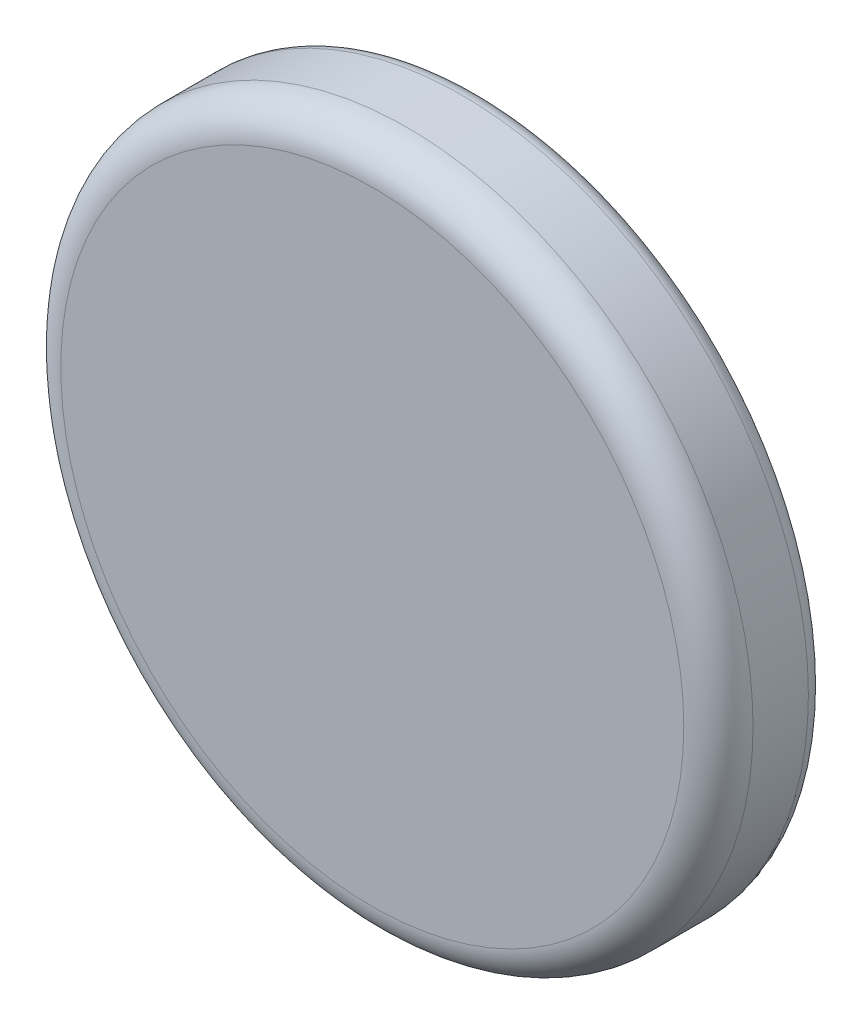
SolidWorks part; units mm, degrees
ref_plane "前视基准面" through (0, 0, 0) normal (0, 0, 1) x (1, 0, 0)
ref_plane "上视基准面" through (0, 0, 0) normal (0, 1, 0) x (1, 0, 0)
ref_plane "右视基准面" through (0, 0, 0) normal (1, 0, 0) x (0, 0, -1)
other "Configuration Table"
sketch "草图1" plane through (0, 0, 0) normal (0, 0, 1) x (1, 0, 0)
  line L0 (-2.5, 0) -> (2.5, 0) construction
  line L1 (0, -2.5) -> (0, 2.5) construction
  line L8 (-0.3703, -2) -> (0.3703, -2)
  line L13 (-0.3703, -2) -> (-0.3703, -0.3359)
  line L14 (-0.3703, 2) -> (0.3703, 2)
  line L54 (0.3703, -2) -> (0.3703, -0.3359)
  line L55 (-0.3703, -2) -> (0.3703, 2) construction
  line L56 (-0.3703, 2) -> (0.3703, -2) construction
  line L57 (-2, -0.3359) -> (-0.3703, -0.3359)
  line L58 (-2, -0.3359) -> (-2, 0.3359)
  line L59 (-2, 0.3359) -> (-0.3703, 0.3359)
  line L60 (2, -0.3359) -> (2, 0.3359)
  line L61 (-2, -0.3359) -> (2, 0.3359) construction
  line L62 (-2, 0.3359) -> (2, -0.3359) construction
  line L70 (-0.3703, 0.3359) -> (-0.3703, 2)
  line L71 (0.3703, 0.3359) -> (0.3703, 2)
  line L72 (0.3703, 0.3359) -> (2, 0.3359)
  line L73 (0.3703, -0.3359) -> (2, -0.3359)
  line L90 (0.5703, 0.5359) -> (0.5703, 2.2)
  line L91 (-0.5703, 2.2) -> (0.5703, 2.2)
  line L92 (-0.5703, 0.5359) -> (-0.5703, 2.2)
  line L93 (-2.2, 0.5359) -> (-0.5703, 0.5359)
  line L94 (-2.2, -0.5359) -> (-2.2, 0.5359)
  line L95 (-2.2, -0.5359) -> (-0.5703, -0.5359)
  line L96 (-0.5703, -2.2) -> (-0.5703, -0.5359)
  line L97 (-0.5703, -2.2) -> (0.5703, -2.2)
  line L98 (0.5703, -2.2) -> (0.5703, -0.5359)
  line L99 (0.5703, -0.5359) -> (2.2, -0.5359)
  line L100 (2.2, -0.5359) -> (2.2, 0.5359)
  line L101 (0.5703, 0.5359) -> (2.2, 0.5359)
  circle A5 centre (0, 0) radius 10
  circle A7 centre (0, 0) radius 9
  circle A9 centre (0, 0) radius 2.5
  point P5 (0, 0)
  point P6 (0, 0)
  point P8 (0, 0)
  point P10 (0, 0)
  dimension "D1" = 5
  dimension "D7" = 20
  dimension "D3" = 4
  dimension "D4" = 0.2
  dimension "D2" = 4
  dimension "D5" = 1.0717
  dimension "D9" = 1
extrude "凸台-拉伸19" add sketch "草图1" against normal blind 2.1 contours A9 L90 L101 L100 L99 L98 L97 L96 L95 L94 L93 L92 L91 region at (-2.4293, 0, 0)
extrude "凸台-拉伸20" add sketch "草图1<24>" along normal blind 1 contours L54 L73 L60 L72 L71 L14 L70 L59 L58 L57 L13 L8 | L101 L90 L91 L92 L93 L94 L95 L96 L97 L98 L99 L100 L73 L54 L8 L13 L57 L58 L59 L70 L14 L71 L72 L60 | A9 L90 L101 L100 L99 L98 L97 L96 L95 L94 L93 L92 L91 | A7 A9 region at (0, 0, 0) region at (1.3852, 0.4736, 0) region at (-8.7454, 0, 0) region at (-2.4293, 0, 0)
sketch "草图1<24>" plane through (0, 0, 0) normal (0, 0, 1) x (1, 0, 0) same geometry as "草图1"
extrude "凸台-拉伸21" add sketch "草图1<25>" along normal blind 1 and the other way blind 2.1 contours A5 A7 region at (-9.7172, 0, 0)
sketch "草图1<25>" plane through (0, 0, 0) normal (0, 0, 1) x (1, 0, 0) same geometry as "草图1"
fillet "圆角1" radius 1 1 edges at (10, 0, 1)
fillet "圆角2" radius 0.5 1 edges at (10, 0, -2.1) type face fillet first side face at (10, 0, 0) second side face at (9, 0, -2.1)
fillet "圆角3" radius 0.5 1 edges at (9, 0, -2.1) type face fillet first side face at (9, 0, -2.1) second side face at (9.5, 0, -2.1)
fillet "圆角4" radius 1 1 edges at (9, 0, 0)
